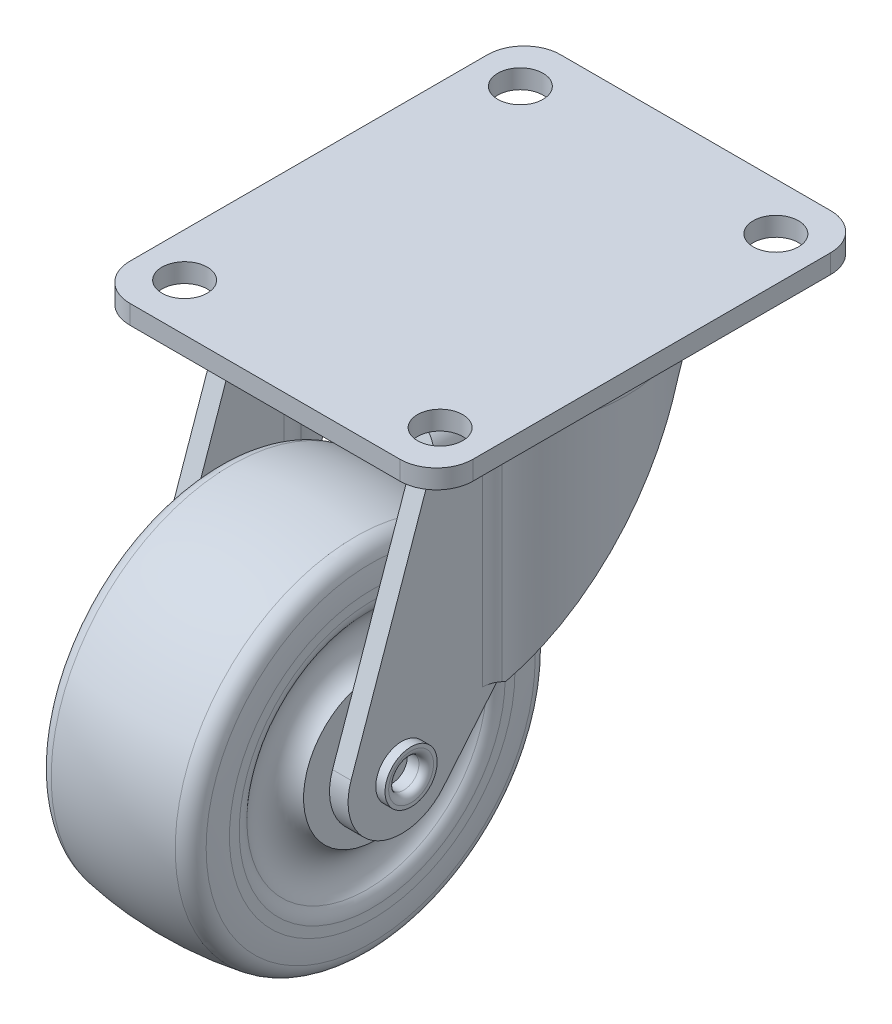
SolidWorks part; units mm, degrees
ref_plane "FRONT" through (0, 0, 0) normal (0, 0, 1) x (1, 0, 0)
ref_plane "TOP" through (0, 0, 0) normal (0, 1, 0) x (1, 0, 0)
ref_plane "RIGHT" through (0, 0, 0) normal (1, 0, 0) x (0, 0, -1)
sketch "Sketch1" plane through (0, 0, 0) normal (0, 1, 0) x (1, 0, 0)
  circle A0 centre (0, 0) radius 20
  dimension "D1" = 40
extrude "Base-Extrude" add sketch "Sketch1" against normal blind 33.02 from offset 5.588 offset against normal yes
sketch "Sketch2" plane through (0, 0, 0) normal (1, 0, 0) x (0, 0, -1)
  line L0 (-20.32, -5.588) -> (0, -5.588)
  line L1 (0, -38.608) -> (0, -5.588) construction
  line L2 (-20.32, -5.588) -> (-32.5552, -40.6746)
  line L3 (20, -5.588) -> (-20, -5.588) construction
  line L4 (-19.9388, -47.8127) -> (0, -23.8607)
  line L5 (0, 0) -> (0, -122.9181) construction
  line L6 (22, 0) -> (-22, 0) construction
  line L7 (0, 18.161) -> (0, -18.161) construction
  line L8 (0, -5.588) -> (0, -23.8607)
  line L9 (0, -23.8607) -> (10.348, -11.43) construction
  line L10 (10.348, -11.43) -> (22.032, -11.43) construction
  line L11 (20, -38.608) -> (20, -5.588) construction
  arc A0 (-32.5552, -40.6746) -> (-19.9388, -47.8127) centre (-25.6, -43.1) ccw
  circle A1 centre (-25.6, -43.1) radius 25.4 construction
  dimension "D5" = 14.732
  dimension "D7" = 68.5
  dimension "D1" = 50.8
  dimension "D4" = 51
  dimension "D2" = 20.32
  dimension "D3" = 9.652
  dimension "D6" = 11.43
extrude "Boss-Extrude1" add sketch "Sketch2" along normal mid plane 29.718
sketch "Sketch3" plane through (0, 0, 0) normal (1, 0, 0) x (0, 0, -1)
  line L0 (-19.9388, -47.8127) -> (-12.2764, -38.608) construction
  line L1 (-64.7142, -101.6) -> (10.348, -11.43)
  line L2 (38.1, -11.43) -> (38.1, -101.6)
  line L3 (-64.7142, -101.6) -> (38.1, -101.6)
  line L4 (10.348, -11.43) -> (22.032, -11.43) construction
  line L6 (10.348, -11.43) -> (38.1, -11.43)
  dimension "D1" = 38.1
  dimension "D2" = 101.6
extrude "Cut-Extrude1" cut sketch "Sketch3" against normal mid plane 76.2
fillet "Fillet1" radius 3.175 5 edges at (0, -5.588, -20) (-14.859, -5.588, 16.8535) (14.859, -5.588, 16.8535) (14.859, -22.098, 13.3869) (-14.859, -22.098, 13.3869)
fillet "Fillet2" radius 4.064 1 edges at (0, -11.43, -10.348)
shell "Shell1" thickness 2.54 removed face at (0, -34.5685, 8.9137) removed face at (0, -18.1227, 24.691) removed face at (0, -46.8773, 27.7371) removed face at (0.0625, -12.0291, -10.5342) removed face at (0, -11.43, -16.1264)
ref_plane "Plane1" through (0, 0, 25.6) normal (0, 0, 1) x (1, 0, 0)
sketch "Sketch4" plane through (-12.319, 0, 0) normal (1, 0, 0) x (0, 0, -1)
  circle A0 centre (-25.6, -43.1) radius 3.175
  arc A3 (-32.5552, -40.6746) -> (-19.9388, -47.8127) centre (-25.6, -43.1) ccw construction
  dimension "D1" = 6.35
extrude "Boss-Extrude2" add sketch "Sketch4" along normal up to next
sketch "Sketch6" plane through (0, 0, 25.6) normal (0, 0, 1) x (1, 0, 0)
  line L1 (11.303, -46.275) -> (-11.303, -46.275)
  line L2 (-12.319, -46.275) -> (12.319, -46.275) construction
  line L3 (-10.795, -61.3205) -> (-10.795, -62.658)
  line L4 (0, -43.1) -> (-22.4069, -43.1) construction
  line L5 (12.319, -43.1) -> (-12.319, -43.1) construction
  line L6 (-12.319, -43.1) -> (-14.859, -43.1) construction
  line L7 (0, -43.1) -> (0, -68.5) construction
  line L8 (-11.303, -46.275) -> (-11.303, -53.006)
  line L9 (11.303, -46.275) -> (11.303, -53.006)
  line L10 (8.89, -46.6778) -> (8.89, -54.0284) construction
  line L12 (10.795, -61.3205) -> (10.795, -62.658)
  arc A0 (-8.4953, -67.7846) -> (8.4953, -67.7846) centre (0, -17.7) ccw
  arc A1 (11.303, -53.006) -> (10.0582, -59.5316) centre (12.917, -56.6954) ccw
  arc A2 (10.795, -62.658) -> (10.5856, -65.6359) centre (-10.4796, -62.658) cw
  arc A3 (10.0582, -59.5316) -> (10.795, -61.3205) centre (8.255, -61.3205) cw
  arc A4 (10.5856, -65.6359) -> (8.4953, -67.7846) centre (8.0706, -65.2804) cw
  arc A5 (-10.5856, -65.6359) -> (-8.4953, -67.7846) centre (-8.0706, -65.2804) ccw
  arc A6 (-10.795, -62.658) -> (-10.5856, -65.6359) centre (10.4796, -62.658) ccw
  arc A7 (-10.0582, -59.5316) -> (-10.795, -61.3205) centre (-8.255, -61.3205) ccw
  arc A8 (-11.303, -53.006) -> (-10.0582, -59.5316) centre (-12.917, -56.6954) cw
  point P19 (10.795, -60.118)
  point P22 (10.2469, -67.4558)
  point P24 (0, -68.5)
  point P37 (0, -46.275)
  dimension "D4" = 21.59
  dimension "D9" = 2.54
  dimension "D6" = 50.8
  dimension "D1" = 22.606
  dimension "D2" = 19.812
  dimension "D3" = 2.413
  dimension "D5" = 7.112
  dimension "D7" = 2.54
  dimension "D8" = 10.2469
revolve "Boss-Revolve1" add sketch "Sketch6" angle 360 about L4
sketch "Sketch12" plane through (0, 0, 0) normal (1, 0, 0) x (0, 0, -1)
  circle A0 centre (-25.6, -43.1) radius 3.5736
extrude "Extrude1" add sketch "Sketch12" along normal mid plane 32.258
sketch "Sketch8" plane through (0, 0, 0) normal (1, 0, 0) x (0, 0, -1)
  line L0 (0, 25.4) -> (0, -13.5012) construction
  line L1 (10.8363, -10.9612) -> (11.43, -10.9612)
  line L2 (3.81, 0) -> (13.081, 0)
  line L3 (16.825, -5.588) -> (-10.5671, -5.588) construction
  line L4 (0, 25.4) -> (0, -13.5012)
  line L5 (15.621, -2.54) -> (15.621, -3.81)
  line L6 (0, -13.5012) -> (3.5645, -13.5012)
  line L7 (0, 25.4) -> (3.81, 25.4)
  line L8 (15.875, -3.81) -> (15.621, -3.81)
  line L9 (0, 0) -> (0, 58.0131) construction
  line L10 (3.81, 25.4) -> (3.81, 0)
  line L11 (15.875, -3.81) -> (15.875, -5.588)
  line L12 (22, 0) -> (-22, 0) construction
  line L13 (0, -38.608) -> (0, -8.763) construction
  line L14 (15.875, -5.588) -> (6.35, -5.588)
  line L15 (6.35, -5.588) -> (6.35, -10.9612)
  line L16 (11.43, -10.9612) -> (11.43, -13.5012)
  line L20 (6.35, -10.9612) -> (4.1581, -10.9612)
  arc A0 (15.621, -2.54) -> (13.081, 0) centre (13.081, -2.54) ccw
  arc A1 (3.5645, -13.5012) -> (11.43, -13.5012) centre (7.4972, -4.826) ccw
  arc A11 (4.1581, -10.9612) -> (10.8363, -10.9612) centre (7.4972, -4.826) ccw
  dimension "D6" = 39.751
  dimension "D8" = 9.525
  dimension "D2" = 2.54
  dimension "D3" = 0.254
  dimension "D4" = 25.4
  dimension "D5" = 7.62
  dimension "D7" = 22.86
  dimension "D9" = 5.3732
  dimension "D11" = 12.7
  dimension "D12" = 31.75
  dimension "D13" = 1.778
  dimension "D10" = 2.54
revolve "Boss-Revolve2" [suppressed] add sketch "Sketch8" angle 360 about L9
chamfer "Chamfer1" [suppressed] distance 1.016 angle 45
sketch "Sketch9" [suppressed] plane through (0, 25.4, 0) normal (0, 1, 0) x (-1, 0, 0)
  line L1 (0, 7.3323) -> (-6.35, 3.6662)
  line L2 (-6.35, 3.6662) -> (-6.35, -3.6662)
  line L3 (-6.35, -3.6662) -> (0, -7.3323)
  line L4 (0, -7.3323) -> (6.35, -3.6662)
  line L5 (6.35, -3.6662) -> (6.35, 3.6662)
  line L6 (6.35, 3.6662) -> (0, 7.3323)
  circle A0 centre (0, 0) radius 6.35 construction
  circle A1 centre (0, 0) radius 3.81 construction
  circle A2 centre (0, 0) radius 3.81
  dimension "D1" = 12.7
extrude "Boss-Extrude3" [suppressed] add sketch "Sketch9" against normal blind 7.7978 from offset 1.27 offset against normal yes
sketch "Sketch10" [suppressed] plane through (0, 6.8128, 0.1695) normal (1, 0, 0) x (0, 0, -1)
  line L0 (0.1695, 0) -> (0.1695, 22.4951) construction
  line L3 (-8.6869, 9.5194) -> (-5.6389, 9.5194)
  line L5 (-8.6869, 17.3172) -> (-5.6389, 17.3172)
  line L7 (-7.1629, 16.4373) -> (-7.1629, 10.3992)
  line L8 (-8.6869, 17.3172) -> (-8.6869, 9.5194)
  line L9 (-5.6389, 17.3172) -> (-7.1629, 16.4373)
  line L10 (-5.6389, 9.5194) -> (-7.1629, 10.3992)
  line L11 (0.1695, 12.5775) -> (0.1695, -26.2032) construction
  line L12 (-7.1629, 9.5194) -> (-7.1629, 17.3172) construction
  line L13 (-7.1629, 13.4183) -> (-8.6869, 13.4183) construction
  line L14 (-7.1629, 17.3172) -> (-3.4967, 17.3172) construction
  dimension "D1" = 0.8799
  dimension "D2" = 1.524
  dimension "D3" = 1.524
revolve "Cut-Revolve1" [suppressed] cut sketch "Sketch10" angle 360 about L0
sketch "Sketch15" plane through (0, -5.588, 0) normal (0, 1, 0) x (1, 0, 0)
  circle A0 centre (0, 0) radius 15
  dimension "D1" = 30
extrude "Boss-Extrude4" add sketch "Sketch15" along normal blind 0.703
sketch "Sketch16" plane through (0, -4.885, 0) normal (0, 1, 0) x (1, 0, 0)
  line L1 (-23.5, -29.5) -> (23.5, -29.5)
  line L2 (-23.5, -29.5) -> (-23.5, 29.5)
  line L3 (-23.5, 29.5) -> (23.5, 29.5)
  line L4 (23.5, -29.5) -> (23.5, 29.5)
  line L5 (-23.5, -29.5) -> (23.5, 29.5) construction
  line L6 (-23.5, 29.5) -> (23.5, -29.5) construction
  point P0 (0, 0)
  dimension "D1" = 47
  dimension "D2" = 59
extrude "Boss-Extrude5" add sketch "Sketch16" along normal blind 2.6
sketch "Sketch17" plane through (0, -2.285, 0) normal (0, 1, 0) x (1, 0, 0)
  line L0 (0, -29.5) -> (0, 29.5) construction
  line L1 (23.5, 29.5) -> (-23.5, 29.5) construction
  line L2 (-23.5, 0) -> (23.5, 0) construction
  line L3 (23.5, -29.5) -> (23.5, 29.5) construction
  circle A0 centre (-17.5, 23) radius 3.1
  circle A1 centre (17.5, 23) radius 3.1
  circle A2 centre (17.5, -23) radius 3.1
  circle A3 centre (-17.5, -23) radius 3.1
  point P6 (0, 0)
  point P11 (0, 0)
  dimension "D3" = 6.2
  dimension "D1" = 35
  dimension "D2" = 46
extrude "Cut-Extrude2" cut sketch "Sketch17" against normal blind 2.6
fillet "Fillet3" radius 5 4 edges at (-23.5, -3.585, -29.5) (-23.5, -3.585, 29.5) (23.5, -3.585, 29.5) (23.5, -3.585, -29.5)
sketch "Sketch18" plane through (16.129, 0, 0) normal (1, 0, 0) x (0, 0, -1)
  circle A2 centre (-25.6, -43.1) radius 2.0736
  circle A3 centre (-25.6, -43.1) radius 2.0736
  dimension "D1" = 1.5
extrude "Cut-Extrude3" cut sketch "Sketch18" against normal blind 2.6
fillet "Fillet4" radius 1 1 edges at (16.129, -43.1, 23.5264)
fillet "Fillet5" radius 1 1 edges at (-16.129, -43.1, 22.0264)
fillet "Fillet6" radius 10 1 edges at (-11.303, -43.1, 15.694)
sketch "Sketch13" [suppressed] plane through (14.859, 0, 0) normal (1, 0, 0) x (0, 0, -1)
  line L0 (-51, -43.1) -> (29.5, -43.1) construction
  line L1 (20, -11.43) -> (20, -43.1) construction
  line L2 (-25.6, -67.7846) -> (-25.6, -2.285) construction
  line L3 (0, -2.285) -> (-25.6, -2.285) construction
  line L5 (-24.5, -2.285) -> (24.5, -2.285) construction
  line L6 (29.5, -2.285) -> (29.5, -43.1) construction
  circle A0 centre (-25.6, -43.1) radius 25.4 construction
  circle A1 centre (-25.6, -43.1) radius 24.6846 construction
  circle A2 centre (-25.6, -43.1) radius 24.6846 construction
  point P11 (0, -2.285)
  dimension "D1" = 71
  dimension "D2" = 65.4996
  dimension "D3" = 80.5
  dimension "D4" = 9.5
